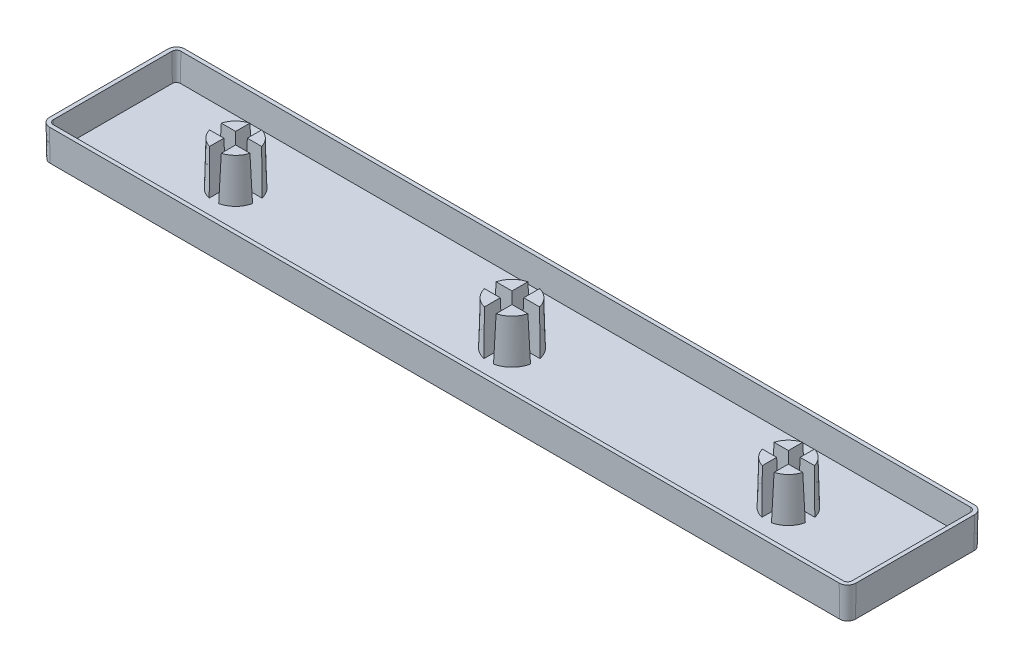
SolidWorks part; units mm, degrees
ref_plane "Front Plane" through (0, 0, 0) normal (0, 0, 1) x (1, 0, 0)
ref_plane "Top Plane" through (0, 0, 0) normal (0, 1, 0) x (1, 0, 0)
ref_plane "Right Plane" through (0, 0, 0) normal (1, 0, 0) x (0, 0, -1)
sketch "Sketch1" plane through (0, 0, 0) normal (0, 1, 0) x (1, 0, 0)
  line L1 (-50, -8.5) -> (50, -8.5)
  line L2 (-51, -7.5) -> (-51, 7.5)
  line L3 (-50, 8.5) -> (50, 8.5)
  line L4 (51, -7.5) -> (51, 7.5)
  line L5 (-51, -8.5) -> (51, 8.5) construction
  line L6 (-51, 8.5) -> (51, -8.5) construction
  arc A0 (-51, 7.5) -> (-50, 8.5) centre (-50, 7.5) cw
  arc A1 (51, 7.5) -> (50, 8.5) centre (50, 7.5) ccw
  arc A2 (51, -7.5) -> (50, -8.5) centre (50, -7.5) cw
  arc A3 (-50, -8.5) -> (-51, -7.5) centre (-50, -7.5) cw
  point P0 (0, 0)
  dimension "D3" = 1
  dimension "D1" = 102
  dimension "D2" = 17
extrude "Boss-Extrude1" add sketch "Sketch1" along normal blind 4 draft 1 draft outward yes
shell "Shell1" thickness 0.5 removed face at (0, 4, 0)
sketch "Sketch2" plane through (0, 0.5, 0) normal (0, 1, 0) x (1, 0, 0)
  line L0 (-54.9388, 0) -> (-37.8078, 0) construction
  line L1 (-2.2, 0) -> (2.2, 0) construction
  line L3 (-0.6, 2.9394) -> (-0.6, 0.6)
  line L4 (-2.9394, 0.6) -> (-0.6, 0.6)
  line L5 (0, -2.2) -> (0, 2.2) construction
  line L6 (-2.9394, -0.6) -> (-0.6, -0.6)
  line L7 (0.6, 2.9394) -> (0.6, 0.6)
  line L8 (-35.6, 2.7429) -> (-35.6, 0.6)
  line L9 (-37.7429, 0.6) -> (-35.6, 0.6)
  line L10 (-34.4, 2.7429) -> (-34.4, 0.6)
  line L11 (-37.7429, -0.6) -> (-35.6, -0.6)
  line L12 (34.4, 2.7429) -> (34.4, 0.6)
  line L13 (32.2571, 0.6) -> (34.4, 0.6)
  line L14 (35, 0.6) -> (35, -0.6) construction
  line L15 (32.2571, -0.6) -> (34.4, -0.6)
  line L16 (35.6, 2.7429) -> (35.6, 0.6)
  line L17 (34.4, -0.6) -> (34.4, -2.7429)
  line L18 (35, 0) -> (35.6, 0) construction
  line L19 (35.6, -0.6) -> (35.6, -2.7429)
  line L20 (37.8078, 0) -> (55.4489, 0) construction
  line L21 (35.6, -0.6) -> (37.7429, -0.6)
  line L22 (35.6, 0.6) -> (37.7429, 0.6)
  line L23 (3, 0) -> (34.4, 0) construction
  line L24 (-0.6, -0.6) -> (-0.6, -2.9394)
  line L25 (0.6, -0.6) -> (0.6, -2.9394)
  line L26 (0.6, 0.6) -> (2.9394, 0.6)
  line L27 (0.6, -0.6) -> (2.9394, -0.6)
  line L28 (-35.6, 0) -> (-34.4, 0) construction
  line L29 (-35.6, -0.6) -> (-35.6, -2.7429)
  line L30 (-34.4, -0.6) -> (-34.4, -2.7429)
  line L31 (-32.1922, 0) -> (-3, 0) construction
  line L32 (-34.4, -0.6) -> (-32.2571, -0.6)
  line L33 (-34.4, 0.6) -> (-32.2571, 0.6)
  line L34 (-35, 0) -> (-35, -0.6) construction
  arc A0 (-2.9394, -0.6) -> (-0.6, -2.9394) centre (0, 0) ccw
  arc A1 (-37.7429, -0.6) -> (-35.6, -2.7429) centre (-35, 0) ccw
  arc A2 (32.2571, -0.6) -> (34.4, -2.7429) centre (35, 0) ccw
  arc A3 (34.4, 2.7429) -> (32.2571, 0.6) centre (35, 0) ccw
  arc A4 (37.7429, 0.6) -> (35.6, 2.7429) centre (35, 0) ccw
  arc A5 (35.6, -2.7429) -> (37.7429, -0.6) centre (35, 0) ccw
  arc A6 (0.6, -2.9394) -> (2.9394, -0.6) centre (0, 0) ccw
  arc A7 (-0.6, 2.9394) -> (-2.9394, 0.6) centre (0, 0) ccw
  arc A8 (2.9394, 0.6) -> (0.6, 2.9394) centre (0, 0) ccw
  arc A9 (-32.2571, 0.6) -> (-34.4, 2.7429) centre (-35, 0) ccw
  arc A10 (-34.4, -2.7429) -> (-32.2571, -0.6) centre (-35, 0) ccw
  arc A11 (-35.6, 2.7429) -> (-37.7429, 0.6) centre (-35, 0) ccw
  dimension "D1" = 35
  dimension "D2" = 35
  dimension "D3" = 0.6
  dimension "D4" = 0.6
  dimension "D6" = 0.6
extrude "Boss-Extrude2" add sketch "Sketch2" along normal blind 5.5 draft 1.5
